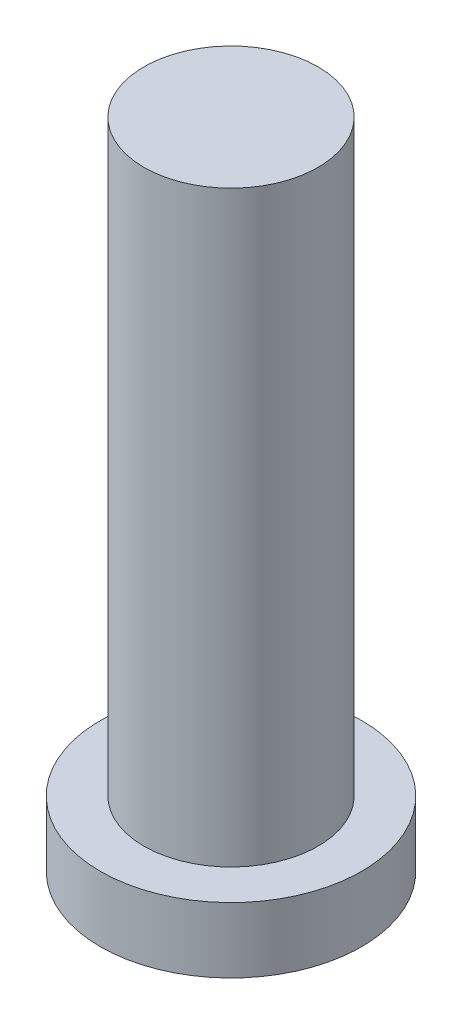
SolidWorks part; units mm, degrees
ref_plane "Front Plane" through (0, 0, 0) normal (0, 0, 1) x (1, 0, 0)
ref_plane "Top Plane" through (0, 0, 0) normal (0, 1, 0) x (1, 0, 0)
ref_plane "Right Plane" through (0, 0, 0) normal (1, 0, 0) x (0, 0, -1)
sketch "Sketch1" plane through (0, 0, 0) normal (0, 1, 0) x (1, 0, 0)
  circle A0 centre (0, 0) radius 3
  dimension "D1" = 6
extrude "Boss-Extrude1" add sketch "Sketch1" along normal blind 1.5
sketch "Sketch2" plane through (0, 1.5, 0) normal (0, 1, 0) x (1, 0, 0)
  circle A0 centre (0, 0) radius 2
  dimension "D1" = 4
extrude "Boss-Extrude2" add sketch "Sketch2" along normal blind 13.5
